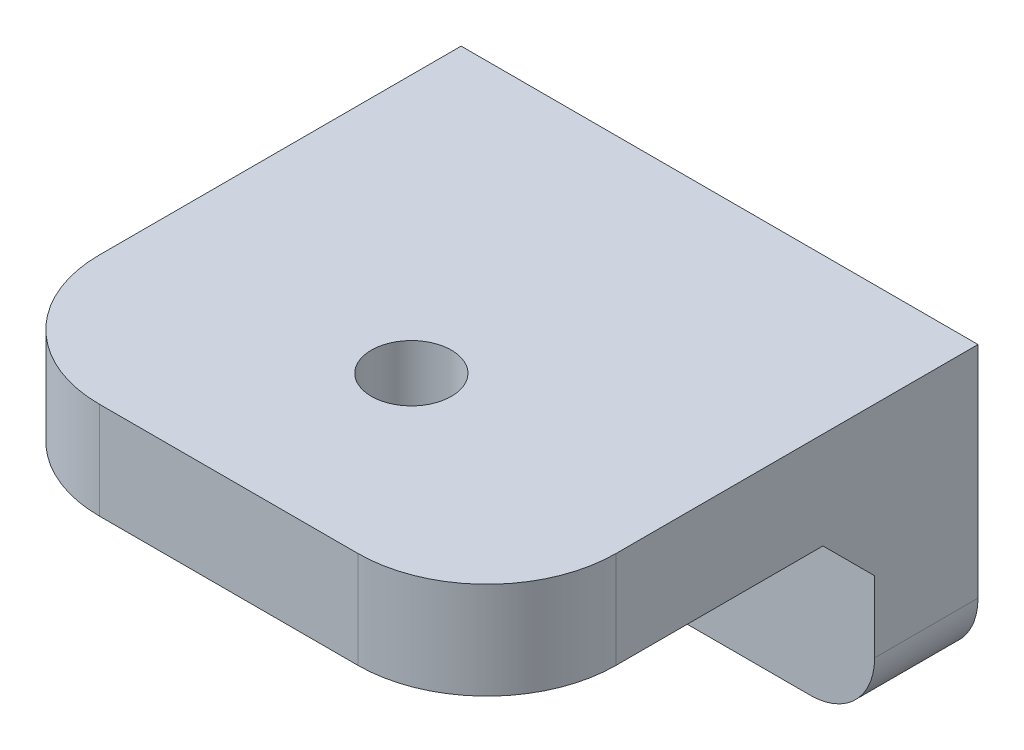
SolidWorks part; units mm, degrees
ref_plane "Front Plane" through (0, 0, 0) normal (0, 0, 1) x (1, 0, 0)
ref_plane "Top Plane" through (0, 0, 0) normal (0, 1, 0) x (1, 0, 0)
ref_plane "Right Plane" through (0, 0, 0) normal (1, 0, 0) x (0, 0, -1)
sketch "Sketch1" plane through (0, 0, 0) normal (0, 0, 1) x (1, 0, 0)
  line L0 (12, -4.4065) -> (14.9129, -4.4065) construction
  line L1 (-20, -4.4065) -> (20, -4.4065)
  line L2 (-20, -4.4065) -> (-20, -26.4065)
  line L3 (-20, -26.4065) -> (20, -26.4065)
  line L4 (20, -4.4065) -> (20, -26.4065)
  line L5 (0, 0) -> (0, -142.8142) construction
  line L6 (-5, -142.8142) -> (5, -142.8142) construction
  dimension "D1" = 0
  dimension "D2" = 20
  dimension "D3" = 20
  dimension "D4" = 22
extrude "Boss-Extrude1" add sketch "Sketch1" along normal blind 8
sketch "Sketch2" plane through (0, 0, 8) normal (0, 0, 1) x (1, 0, 0)
  line L0 (20, -26.4065) -> (20, -4.4065) construction
  line L1 (-20, -4.4065) -> (20, -4.4065)
  line L2 (-20, -4.4065) -> (-20, -11.9065)
  line L3 (-20, -11.9065) -> (20, -11.9065)
  line L4 (20, -4.4065) -> (20, -11.9065)
  dimension "D1" = 7.5
extrude "Boss-Extrude2" add sketch "Sketch2" along normal blind 30
chamfer "Chamfer1" distance 4 angle 45 1 edges at (0, -11.9065, 8)
fillet "Fillet1" radius 10 2 edges at (20, -8.1565, 38) (-20, -8.1565, 38)
fillet "Fillet2" radius 5 2 edges at (20, -26.4065, 4) (-20, -26.4065, 4)
sketch "Sketch3" plane through (0, -4.4065, 0) normal (0, 1, 0) x (1, 0, 0)
  circle A0 centre (0, -23.8518) radius 3.1
extrude "Cut-Extrude1" cut sketch "Sketch3" against normal through all
